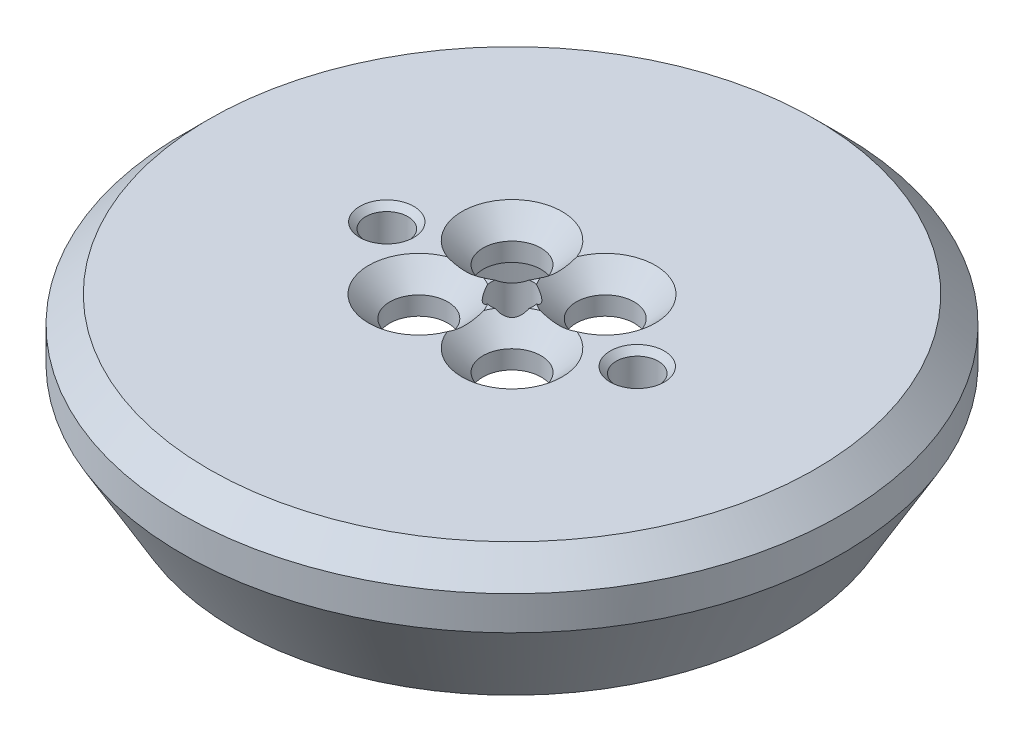
SolidWorks part; units mm, degrees
material "Brass"
ref_plane "Front Plane" through (0, 0, 0) normal (0, 0, 1) x (1, 0, 0)
ref_plane "Top Plane" through (0, 0, 0) normal (0, 1, 0) x (1, 0, 0)
ref_plane "Right Plane" through (0, 0, 0) normal (1, 0, 0) x (0, 0, -1)
sketch "Sketch1" plane through (0, 0, 0) normal (0, 1, 0) x (1, 0, 0)
  circle A0 centre (0, 0) radius 12.5
  dimension "D1" = 25
extrude "Boss-Extrude1" add sketch "Sketch1" along normal blind 1.5
sketch "Sketch2" plane through (0, 1.5, 0) normal (0, 1, 0) x (1, 0, 0)
  circle A0 centre (0, 0) radius 0.8
  dimension "D1" = 1.6
extrude "Cut-Extrude1" cut sketch "Sketch2" against normal through all both and the other way through all
hole_wizard "CSK for M2 Flat Head Machine Screw1" positions "Sketch3" profile "Sketch4" countersink size "M2" standard "ANSI Metric"
sketch "Sketch3" plane through (0, 1.5, 0) normal (0, 1, 0) x (1, 0, 0)
  line L1 (-1.7678, 1.7678) -> (1.7678, 1.7678)
  line L2 (-1.7678, 1.7678) -> (-1.7678, -1.7678)
  line L3 (-1.7678, -1.7678) -> (1.7678, -1.7678)
  line L4 (1.7678, 1.7678) -> (1.7678, -1.7678)
  line L5 (-1.7678, 1.7678) -> (1.7678, -1.7678) construction
  point P0 (-1.7678, 1.7678)
  point P2 (1.7678, 1.7678)
  point P4 (1.7678, -1.7678)
  point P6 (-1.7678, -1.7678)
  point P120 (0, 0)
  dimension "D1" = 5
sketch "Sketch4" plane through (-1.7678, 1.5, -1.7678) normal (1, 0, 0) x (0, 0, 1)
  line L0 (0, 0) -> (0, 5.6609)
  line L1 (0, 5.6609) -> (1.1, 5)
  line L2 (1.1, 5) -> (1.1, 0.8)
  line L3 (1.1, 0.8) -> (1.9, 0)
  line L5 (1.9, 0) -> (0, 0)
  line L6 (-1.1, 0.8) -> (-1.9, 0) construction
  line L10 (0, 5.6609) -> (-1.1, 5) construction
  line L11 (0, -6.35) -> (0, 107.95) construction
  dimension "Hole Dia." = 2.2
  dimension "Hole Depth" = 5
  dimension "Near C'Sink Dia." = 3.8
  dimension "Near C'Sink Angle" = 90
  dimension "Drill Angle" = 118
sketch "Sketch6" plane through (0, 0, 0) normal (0, 0, 1) x (1, 0, 0)
  line L0 (-12.5, 0) -> (-12.5, -1.25)
  line L1 (-12.5, -1.25) -> (-7.2, -1.25)
  line L2 (-7.2, -1.25) -> (-5, 0)
  line L3 (-5, 0) -> (-12.5, 0)
  line L4 (0, 0) -> (0, -5.6432) construction
  dimension "D1" = 1.25
  dimension "D2" = 5
  dimension "D3" = 7.2
revolve "Revolve1" add sketch "Sketch6" angle 360 about L4
sketch "Sketch7" plane through (0, -1.25, 0) normal (0, -1, 0) x (1, 0, 0)
  circle A0 centre (0, 0) radius 7.2 construction
  circle A1 centre (0, 0) radius 12.5
  circle A2 centre (0, 0) radius 12.5
  circle A3 centre (0, 0) radius 7.2
  dimension "D1" = 0
extrude "Boss-Extrude2" add sketch "Sketch7" along normal blind 3
sketch "Sketch11" plane through (0, 1.5, 0) normal (0, 1, 0) x (1, 0, 0)
  line L0 (0, 0) -> (-3.2481, 0) construction
  line L1 (-7.25, 5.1678) -> (-7.25, -5.1678)
  line L2 (-7.25, -5.1678) -> (7.25, -5.1678)
  line L3 (7.25, -5.1678) -> (7.25, 5.1678)
  line L4 (7.25, 5.1678) -> (-7.25, 5.1678)
  line L5 (-7.25, 5.1678) -> (7.25, -5.1678) construction
  line L6 (-1.7678, -3.6678) -> (-1.7678, -5.1678) construction
  line L7 (-0.6889, -3.6678) -> (-2.8466, -3.6678) construction
  circle A0 centre (0, 0) radius 10
  arc A4 (-2.4642, 0) -> (0, -2.4642) centre (-1.7678, -1.7678) ccw construction
  dimension "D1" = 1.5
  dimension "D3" = 20
  dimension "D2" = 14.5
extrude "Boss-Extrude3" [suppressed] add sketch "Sketch11" along normal blind 3
fillet "Fillet2" [suppressed] radius 5
fillet "Fillet3" [suppressed] radius 1
fillet "Fillet1" radius 1 2 edges at (0, 0, 5) (0, -1.25, 7.2)
loft "Loft2" [suppressed] add
sketch "Sketch14" [suppressed] plane through (0, 4.5, 0) normal (0, 1, 0) x (1, 0, 0)
  circle A0 centre (0, 0) radius 10 construction
  circle A1 centre (0, 0) radius 10
extrude "Cut-Extrude2" [suppressed] cut sketch "Sketch14" against normal through all both and the other way through all
combine bodies "Combine1" [suppressed] operation type add bodies to combine 110 107
chamfer "Chamfer1" distance 1 angle 45 1 edges at (0, 1.5, 12.5)
chamfer "Chamfer2" distance 1 angle 45 1 edges at (0, -4.25, -7.2)
chamfer "Chamfer3" distance 2 angle 60 1 edges at (0, -4.25, -12.5) first distance on face at (0, -4.25, -8.2)
hole_wizard "M2x0.4 Tapped Hole1" positions "Sketch8" profile "Sketch9" tap size "M2x0.4" standard "ANSI Metric"
sketch "Sketch8" plane through (0, 1.5, 0) normal (0, 1, 0) x (1, 0, 0)
  line L0 (-4.75, 0) -> (4.75, 0) construction
  point P0 (-4.75, 0)
  point P2 (4.75, 0)
  dimension "D1" = 9.5
sketch "Sketch9" plane through (-4.75, 1.5, 0) normal (1, 0, 0) x (0, 0, 1)
  line L0 (0, 0) -> (0, 5.6807)
  line L1 (0, 5.6807) -> (0.8, 5.2)
  line L2 (0.8, 5.2) -> (0.8, 0.225)
  line L3 (0.8, 0.225) -> (1.025, 0)
  line L5 (1.025, 0) -> (0, 0)
  line L6 (-0.8, 0.225) -> (-1.025, 0) construction
  line L10 (0, 5.6807) -> (-0.8, 5.2) construction
  line L11 (0, -6.35) -> (0, 107.95) construction
  dimension "Tap Drill Dia." = 1.6
  dimension "Tap Drill Depth" = 5.2
  dimension "Near C'Sink Dia." = 2.05
  dimension "Near C'Sink Angle" = 90
  dimension "Drill Angle" = 118
cosmetic thread "Hole Thread1" parameters "D1"=2.4801, "D2"=2
cosmetic thread "Hole Thread2" parameters "D1"=2.4801, "D2"=2
